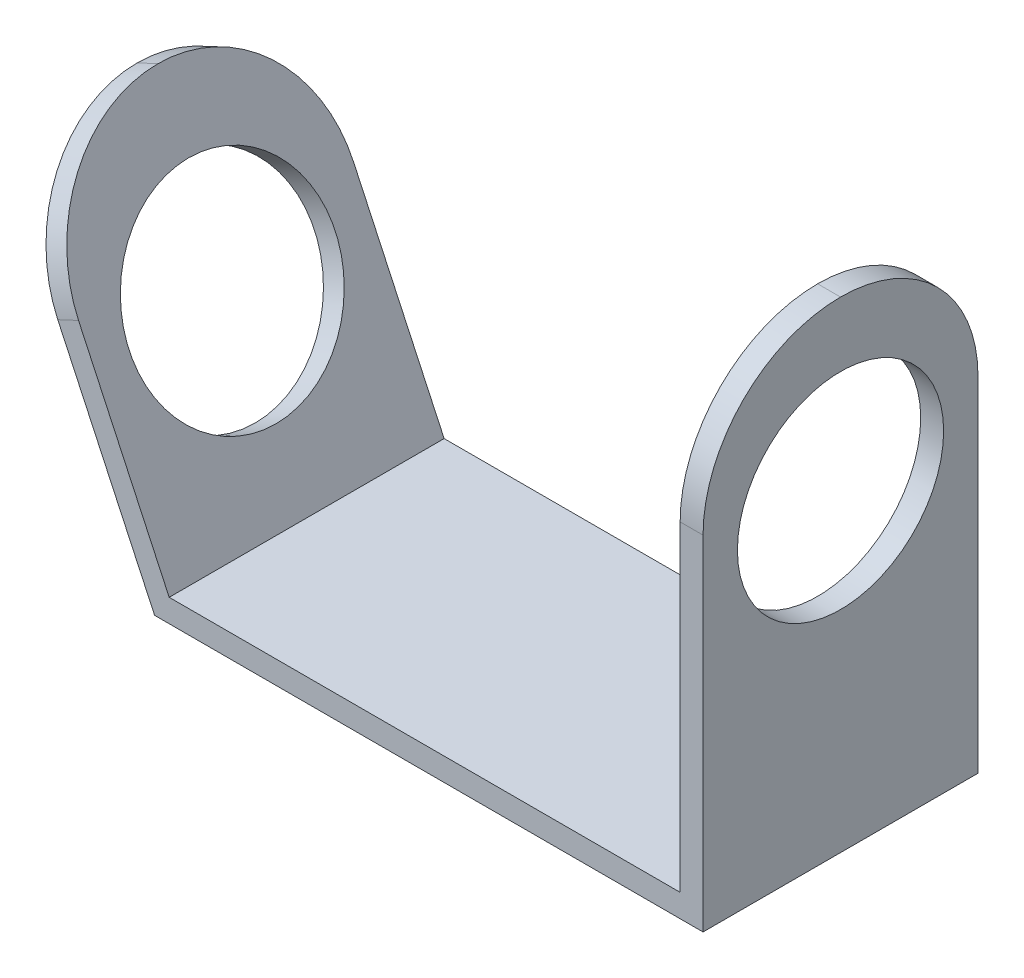
SolidWorks part; units mm, degrees
material "ASTM A36 Acero"
ref_plane "Alzado" through (0, 0, 0) normal (0, 0, 1) x (1, 0, 0)
ref_plane "Planta" through (0, 0, 0) normal (0, 1, 0) x (1, 0, 0)
ref_plane "Vista lateral" through (0, 0, 0) normal (1, 0, 0) x (0, 0, -1)
sketch "Croquis1" plane through (0, 0, 0) normal (0, 0, 1) x (1, 0, 0)
  line L0 (-306.9896, 145.0092) -> (-239.3707, 0)
  line L1 (-239.3707, 0) -> (0, 0)
  line L2 (0, 0) -> (0, 210)
  line L3 (0, 210) -> (-10, 210)
  line L4 (-10, 210) -> (-10, 10)
  line L5 (-10, 10) -> (-233, 10)
  line L6 (-233, 10) -> (-297.9265, 149.2354)
  line L7 (-297.9265, 149.2354) -> (-306.9896, 145.0092)
  line L8 (-119.6854, 10) -> (-119.6854, 0) construction
  dimension "D1" = 115
  dimension "D2" = 223
  dimension "D3" = 10
  dimension "D4" = 200
  dimension "D5" = 160
extrude "Saliente-Extruir1" add sketch "Croquis1" along normal blind 110 and the other way blind 10
sketch "Croquis2" plane through (-10, 0, 0) normal (-1, 0, 0) x (0, 0, 1)
  line L0 (-10, 136.8412) -> (110, 136.8412) construction
  line L1 (-10, 210) -> (-10, 10) construction
  line L2 (110, 210) -> (110, 10) construction
  circle A0 centre (50, 136.8412) radius 45
  point P8 (50, 136.8412)
  dimension "D1" = 90
extrude "Cortar-Extruir1" cut sketch "Croquis2" against normal blind 100
sketch "Croquis3" plane through (-187.5545, -87.4581, 0) normal (0.9063, 0.4226, 0) x (0, 0, -1)
  line L0 (-110, 261.1624) -> (10, 261.1624) construction
  line L1 (-50, 261.1624) -> (-50, 107.5331) construction
  line L2 (-110, 107.5331) -> (10, 107.5331) construction
  circle A0 centre (-50, 184.3478) radius 45
  point P4 (-50, 261.1624)
  dimension "D1" = 90
extrude "Cortar-Extruir2" cut sketch "Croquis3" against normal blind 100
fillet "Fillet1" radius 60 4 edges at (-5, 210, 110) (-5, 210, -10) (-302.4581, 147.1223, -10) (-302.4581, 147.1223, 110)
